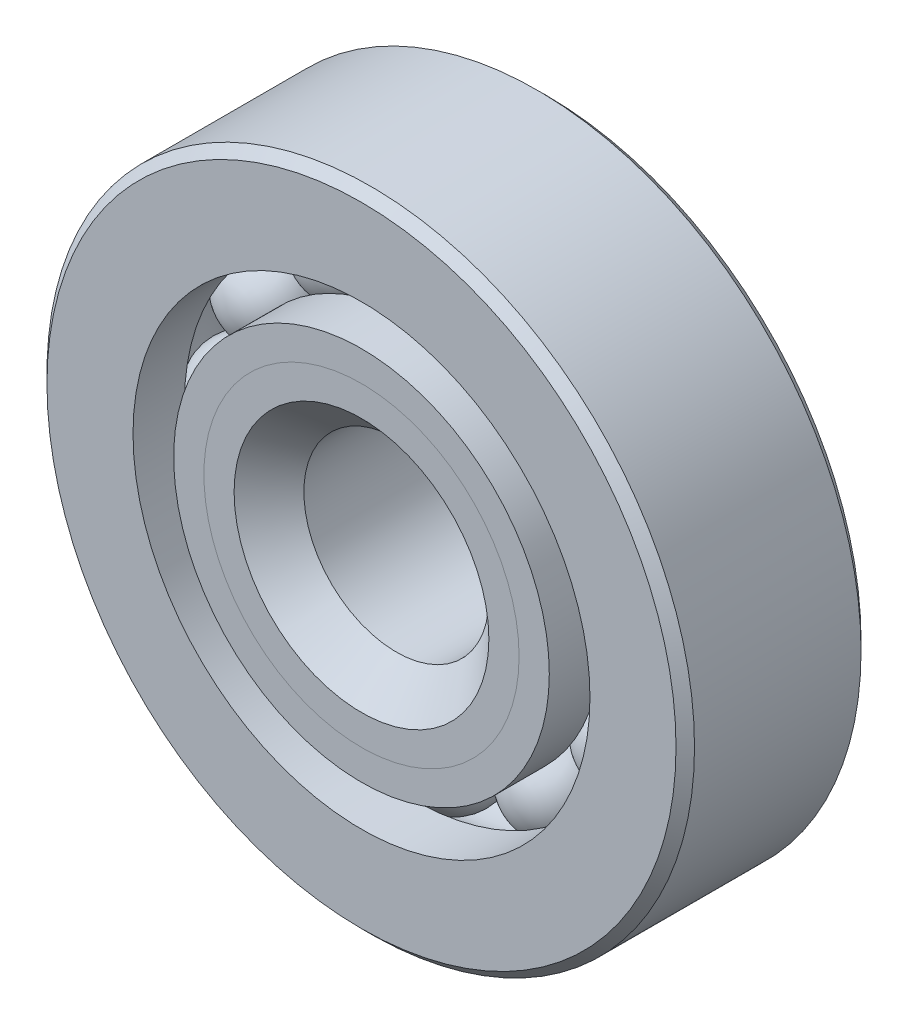
SolidWorks part; units mm, degrees
ref_plane "Front Plane" through (0, 0, 0) normal (0, 0, 1) x (1, 0, 0)
ref_plane "Top Plane" through (0, 0, 0) normal (0, 1, 0) x (1, 0, 0)
ref_plane "Right Plane" through (0, 0, 0) normal (1, 0, 0) x (0, 0, -1)
sketch "Sketch1" plane through (0, 0, 0) normal (1, 0, 0) x (0, 0, -1)
  line L0 (-3.175, 0) -> (3.175, 0) construction
  line L1 (0, 11.1125) -> (0, -11.1125) construction
  line L2 (2.8575, 11.1125) -> (-2.8575, 11.1125)
  line L3 (-2.8575, 11.1125) -> (-3.175, 10.795)
  line L4 (-3.175, 10.795) -> (-3.175, 7.8416)
  line L5 (-3.175, 7.8416) -> (-1.4111, 7.8416)
  line L6 (3.175, 7.8416) -> (1.4111, 7.8416)
  line L7 (3.175, 10.795) -> (3.175, 7.8416)
  line L8 (2.8575, 11.1125) -> (3.175, 10.795)
  line L9 (0, 11.1125) -> (0, 7.1438) construction
  line L10 (0, 7.1438) -> (0, 3.175) construction
  arc A0 (-1.4111, 7.8416) -> (1.4111, 7.8416) centre (0, 7.1438) cw
  point P14 (0, 3.175)
  dimension "D3" = 2.8222
  dimension "D1" = 45
  dimension "Width" = 6.35
  dimension "OD" = 22.225
  dimension "D2" = 0.3175
  dimension "Shaft Dia" = 6.35
  dimension "D4" = 0.6978
revolve "Revolve1" add sketch "Sketch1" angle 360 about L0
sketch "Sketch2" plane through (0, 0, 0) normal (1, 0, 0) x (0, 0, -1)
  line L0 (-3.175, 6.4459) -> (-1.4111, 6.4459)
  line L1 (-3.175, 10.795) -> (-3.175, -10.795) construction
  line L2 (-3.175, 6.4459) -> (-3.175, 5.4091)
  line L3 (-3.175, 5.4091) -> (-2.1382, 4.3723)
  line L4 (-2.1382, 4.3723) -> (0, 4.3723)
  line L5 (0, 11.1125) -> (0, -11.1125) construction
  line L6 (0, 4.3723) -> (0, 5.5695)
  line L7 (0, 5.5695) -> (0, 3.175) construction
  line L8 (-3.175, 6.4459) -> (-3.175, 4.3723) construction
  line L9 (-3.175, 4.3723) -> (-2.1382, 4.3723) construction
  arc A0 (-1.4111, 6.4459) -> (0, 5.5695) centre (0, 7.1438) ccw
  arc A1 (1.4111, 7.8416) -> (-1.4111, 7.8416) centre (0, 7.1438) ccw construction
  circle A2 centre (0, 7.1438) radius 1.5742 construction
  dimension "D1" = 45
revolve "Revolve2" add sketch "Sketch2" angle 360 about L0
sketch "Sketch3" plane through (0, 0, 0) normal (1, 0, 0) x (0, 0, -1)
  line L0 (-3.175, 5.4091) -> (-2.1382, 4.3723)
  line L1 (-2.1382, 4.3723) -> (0, 4.3723)
  line L2 (0, 4.3723) -> (0, 5.5695)
  line L3 (-3.175, 5.4091) -> (-3.175, 4.3723)
  line L4 (-3.175, 6.4459) -> (-3.175, 4.3723) construction
  line L5 (-3.175, 4.3723) -> (-1.9777, 3.175)
  line L6 (-1.9777, 3.175) -> (2.8575, 3.175)
  line L7 (2.8575, 11.1125) -> (2.8575, -11.1125) construction
  line L8 (2.8575, 3.175) -> (3.175, 3.4925)
  line L9 (3.175, -10.795) -> (3.175, 10.795) construction
  line L10 (3.175, 3.4925) -> (3.175, 6.4459)
  line L11 (3.175, 6.4459) -> (1.4111, 6.4459)
  line L13 (2.8575, 11.1125) -> (3.175, 10.795) construction
  circle A0 centre (0, 7.1438) radius 1.5742 construction
  arc A1 (1.4111, 6.4459) -> (0, 5.5695) centre (0, 7.1438) cw
revolve "Revolve3" add sketch "Sketch3" angle 360 about L0
sketch "Sketch4" plane through (0, 0, 0) normal (1, 0, 0) x (0, 0, -1)
  line L0 (-1.5742, 7.1438) -> (1.5742, 7.1438)
  circle A1 centre (0, 7.1438) radius 1.5742 construction
  arc A2 (-1.5742, 7.1438) -> (1.5742, 7.1438) centre (0, 7.1438) cw
  arc A3 (1.4111, 7.8416) -> (-1.4111, 7.8416) centre (0, 7.1438) ccw construction
revolve "Revolve4" add sketch "Sketch4" angle 360 about L0
ref_axis "Axis1" through (0, 0, -3.175) along (0, 0, 1)
pattern_circular "CirPattern1" count 12 every 30 about axis through (0, 0, -3.175) along (0, 0, 1) of bodies 104
equation "\"D2@Sketch1\" = \"Width@Sketch1\"*.05"
equation "\"D3@Sketch1\" = \"Width@Sketch1\"/2.25"
equation "\"D4@Sketch1\" = (((\"OD@Sketch1\"-\"Width@Sketch1\")/2)/3.25)/3.5"
equation "\"D2@CirPattern1\" = 360/\"Balls@CirPattern1\""
